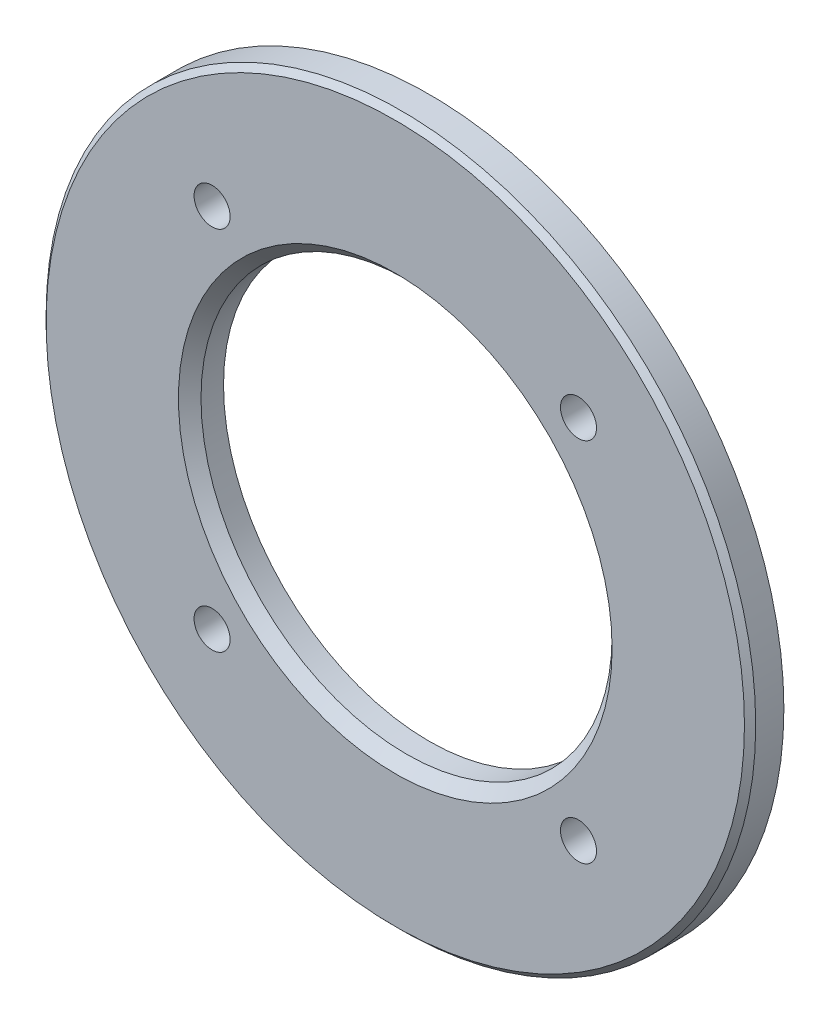
SolidWorks part; units mm, degrees
ref_plane "Спереди" through (0, 0, 0) normal (0, 0, 1) x (1, 0, 0)
ref_plane "Сверху" through (0, 0, 0) normal (0, 1, 0) x (1, 0, 0)
ref_plane "Справа" through (0, 0, 0) normal (1, 0, 0) x (0, 0, -1)
sketch "Эскиз1" plane through (0, 0, 0) normal (0, 0, 1) x (1, 0, 0)
  circle A0 centre (0, 0) radius 31.5
  circle A1 centre (0, 0) radius 18.25
  dimension "D1" = 63
  dimension "D2" = 36.5
extrude "Бобышка-Вытянуть1" add sketch "Эскиз1" along normal blind 3
chamfer "Фаска2" distance 1 angle 45 1 edges at (18.25, 0, 3)
chamfer "Фаска3" distance 0.5 angle 45 1 edges at (31.5, 0, 3)
sketch "Эскиз2" plane through (0, 0, 0) normal (0, 0, -1) x (-1, 0, 0)
  line L0 (0, 0) -> (0, 23) construction
  line L1 (-16.2635, 16.2635) -> (0, 0) construction
  circle A0 centre (0, 0) radius 23 construction
  circle A1 centre (-16.2635, 16.2635) radius 1.6
  dimension "D1" = 46
  dimension "D2" = 45
  dimension "D3" = 3.2
ref_axis "Ось1" through (0, 0, 2) along (0, 0, -1)
extrude "Вырез-Вытянуть1" cut sketch "Эскиз2" against normal through all
pattern_circular "Круговой массив1" count 4 over 360 about axis through (0, 0, 2) along (0, 0, -1) of "Вырез-Вытянуть1"
